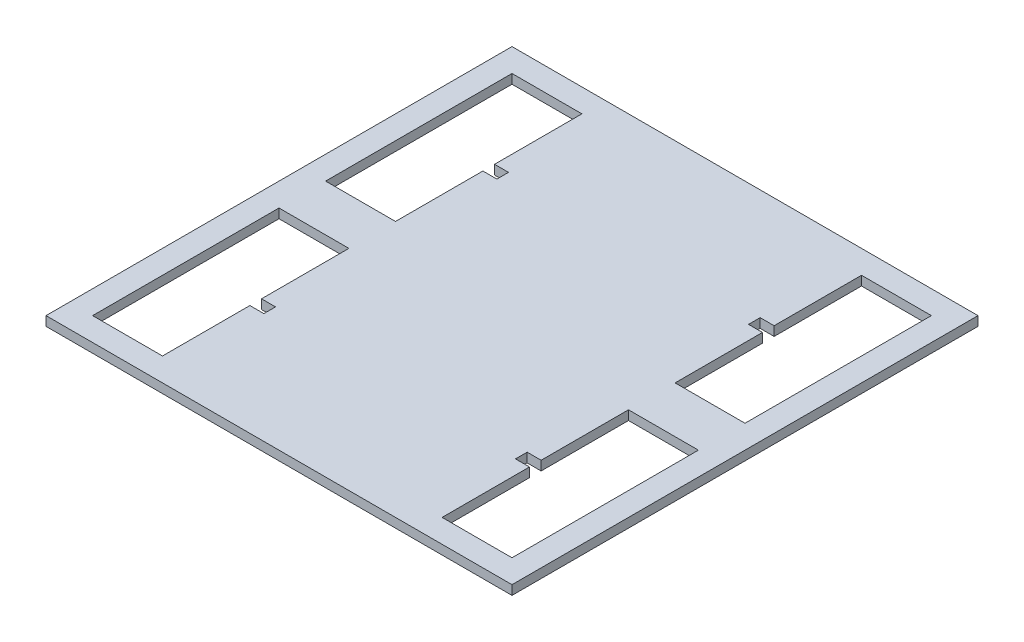
SolidWorks part; units mm, degrees
ref_plane "Front Plane" through (0, 0, 0) normal (0, 0, 1) x (1, 0, 0)
ref_plane "Top Plane" through (0, 0, 0) normal (0, 1, 0) x (1, 0, 0)
ref_plane "Right Plane" through (0, 0, 0) normal (1, 0, 0) x (0, 0, -1)
sketch "Sketch1" plane through (0, 0, 0) normal (0, 1, 0) x (1, 0, 0)
  line L1 (0, 0) -> (400, 0)
  line L2 (0, 0) -> (0, 400)
  line L3 (0, 400) -> (400, 400)
  line L4 (400, 0) -> (400, 400)
  dimension "D1" = 400
  dimension "D2" = 400
base flange "Base-Flange1" sketch "Sketch1" thickness 8 reverse thickness direction no parameters "D1"=45
sketch "Sketch2" plane through (0, 0, 0) normal (0, 1, 0) x (1, 0, 0)
  line L0 (200, 400) -> (200, 0) construction
  line L1 (80, 100) -> (79.9784, 100.0293) construction
  line L2 (400, 400) -> (0, 400) construction
  line L3 (80, 180) -> (20, 20) construction
  line L4 (80, 20) -> (20, 180) construction
  line L5 (80, 295) -> (80, 220)
  line L10 (0, 200) -> (245.4667, 200) construction
  line L11 (0, 400) -> (0, 0) construction
  line L12 (80, 380) -> (20, 380)
  line L13 (80, 380) -> (80, 305)
  line L14 (80, 220) -> (20, 220)
  line L15 (20, 380) -> (20, 220)
  line L16 (80, 380) -> (20, 220) construction
  line L17 (80, 220) -> (20, 380) construction
  line L18 (92, 305) -> (80, 305)
  line L19 (92, 305) -> (92, 295)
  line L20 (92, 295) -> (80, 295)
  line L22 (80, 300) -> (79.9784, 299.9707) construction
  line L23 (92, 105) -> (80, 105)
  line L24 (92, 95) -> (92, 105)
  line L25 (92, 95) -> (80, 95)
  line L26 (20, 20) -> (20, 180)
  line L27 (80, 180) -> (20, 180)
  line L28 (80, 20) -> (80, 95)
  line L29 (80, 20) -> (20, 20)
  line L30 (80, 105) -> (80, 180)
  line L31 (320, 300) -> (320.0216, 299.9707) construction
  line L32 (320, 220) -> (380, 380) construction
  line L33 (320, 380) -> (380, 220) construction
  line L34 (320, 20) -> (380, 180) construction
  line L35 (320, 180) -> (380, 20) construction
  line L36 (320, 100) -> (320.0216, 100.0293) construction
  line L37 (320, 105) -> (320, 180)
  line L38 (320, 20) -> (380, 20)
  line L39 (320, 20) -> (320, 95)
  line L40 (320, 180) -> (380, 180)
  line L41 (380, 20) -> (380, 180)
  line L42 (308, 95) -> (320, 95)
  line L43 (308, 95) -> (308, 105)
  line L44 (308, 105) -> (320, 105)
  line L45 (308, 295) -> (320, 295)
  line L46 (308, 305) -> (308, 295)
  line L47 (308, 305) -> (320, 305)
  line L48 (380, 380) -> (380, 220)
  line L49 (320, 220) -> (380, 220)
  line L50 (320, 380) -> (320, 305)
  line L51 (320, 380) -> (380, 380)
  line L52 (320, 295) -> (320, 220)
  point P2 (92, 300)
  point P3 (0, 0)
  point P6 (0, 0)
  point P7 (0, 0)
  point P15 (50, 300)
  point P33 (50, 100)
  point P34 (92, 100)
  point P55 (308, 100)
  point P56 (350, 100)
  point P57 (350, 300)
  point P58 (308, 300)
  dimension "D1" = 60
  dimension "D2" = 12
  dimension "D3" = 10
  dimension "D6" = 160
  dimension "D7" = 20
extrude "Cut-Extrude1" cut sketch "Sketch2" against normal blind 10 normal cut yes
sketch "Bend-Lines1" [suppressed] plane through (0, 0, 0) normal (0, 1, 0) x (1, 0, 0)
sketch "Bounding-Box1" [suppressed] plane through (0, 0, 0) normal (0, 1, 0) x (1, 0, 0)
sheet metal parameters "Sheet-Metal1" thickness 8 parameters "D1"=45
flat pattern "Flat-Pattern1" [suppressed]
sketch "Bend-Lines2" plane through (0, 0, 0) normal (0, 1, 0) x (1, 0, 0)
sketch3d "Bounding-Box2" [suppressed]
  line L0 (0, 0, 0) -> (0, 400, 0) construction
  line L1 (400, 0, 0) -> (400, 400, 0) construction
  line L2 (0, 0, 0) -> (400, 0, 0) construction
  line L3 (0, 400, 0) -> (400, 400, 0) construction
sheet metal parameters "Sheet-Metal3" thickness 8 parameters "D1"=45
flat pattern "Flat-Pattern1"
sketch "Bend-Lines2" plane through (0, 0, 0) normal (0, 1, 0) x (1, 0, 0)
sketch3d "Bounding-Box2" [suppressed]
  line L0 (0, 0, 0) -> (0, 400, 0) construction
  line L1 (400, 0, 0) -> (400, 400, 0) construction
  line L2 (0, 0, 0) -> (400, 0, 0) construction
  line L3 (0, 400, 0) -> (400, 400, 0) construction
